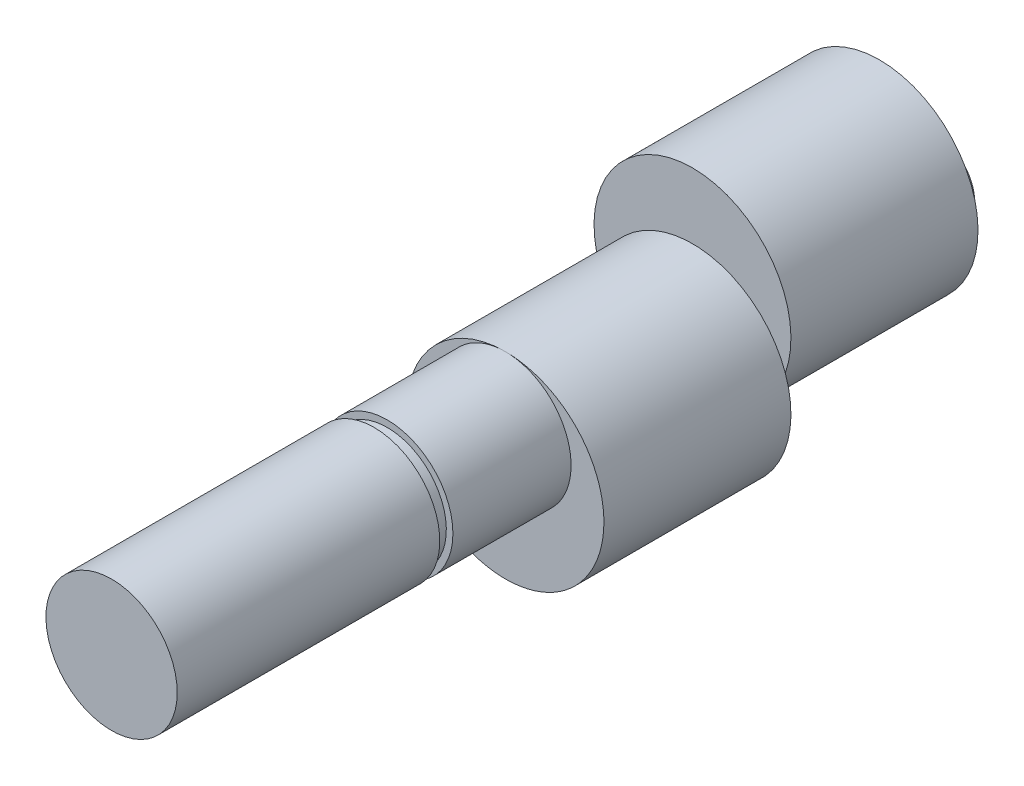
SolidWorks part; units mm, degrees
ref_plane "Front Plane" through (0, 0, 0) normal (0, 0, 1) x (1, 0, 0)
ref_plane "Top Plane" through (0, 0, 0) normal (0, 1, 0) x (1, 0, 0)
ref_plane "Right Plane" through (0, 0, 0) normal (1, 0, 0) x (0, 0, -1)
sketch "Sketch1" plane through (0, 0, 0) normal (0, 0, 1) x (1, 0, 0)
  circle A0 centre (0, 0) radius 7.5 construction
  circle A1 centre (0, -2.5) radius 7.5
  dimension "D1" = 15
  dimension "D2" = 2.5
extrude "Boss-Extrude1" add sketch "Sketch1" along normal blind 14.25
sketch "Sketch2" plane through (0, 0, 0) normal (0, 0, -1) x (-1, 0, 0)
  circle A0 centre (0, 2.5) radius 7.5
  circle A1 centre (0, -2.5) radius 7.5 construction
  dimension "D1" = 2.5
extrude "Boss-Extrude2" add sketch "Sketch2" along normal blind 14.25
sketch "Sketch3" plane through (0, 0, -14.25) normal (0, 0, -1) x (-1, 0, 0)
  circle A0 centre (0, 0) radius 3
  dimension "D1" = 6
extrude "Cut-Extrude1" cut sketch "Sketch3" against normal through all
sketch "Sketch4" plane through (0, 0, -14.25) normal (0, 0, -1) x (-1, 0, 0)
  circle A0 centre (0, 0) radius 3
  circle A1 centre (0, 0) radius 3 construction
extrude "Boss-Extrude3" add sketch "Sketch4" along normal blind 4.25 separate body
extrude "Boss-Extrude4" add sketch "Sketch4<2>" against normal up to surface (28.5 mm away) up to face at (-3, 0, 14.25)
sketch "Sketch4<2>" plane through (0, 0, -14.25) normal (0, 0, -1) x (-1, 0, 0) same geometry as "Sketch4"
sketch "Sketch5" plane through (0, 0, 14.25) normal (0, 0, 1) x (1, 0, 0)
  circle A0 centre (0, 0) radius 5
  circle A1 centre (0, 0) radius 3
  circle A2 centre (0, 0) radius 3 construction
  dimension "D2" = 10
  dimension "D1" = 0
extrude "Boss-Extrude5" add sketch "Sketch5" along normal blind 30
sketch "Sketch7" plane through (0, 0, 0) normal (1, 0, 0) x (0, 0, -1)
  line L0 (-14.25, 5) -> (-14.25, -10) construction
  line L1 (-24.25, 6.7915) -> (-23.25, 6.7915)
  line L2 (-24.25, 6.7915) -> (-24.25, 4.5)
  line L3 (-24.25, 4.5) -> (-23.25, 4.5)
  line L4 (-23.25, 6.7915) -> (-23.25, 4.5)
  line L5 (-14.25, 5) -> (-44.25, 5) construction
  line L6 (-44.25, 0) -> (0, 0) construction
  line L7 (-44.25, 5) -> (-44.25, -5) construction
  dimension "D1" = 10
  dimension "D2" = 1
  dimension "D3" = 0.5
revolve "Cut-Revolve1" cut sketch "Sketch7" angle 360 about L6
